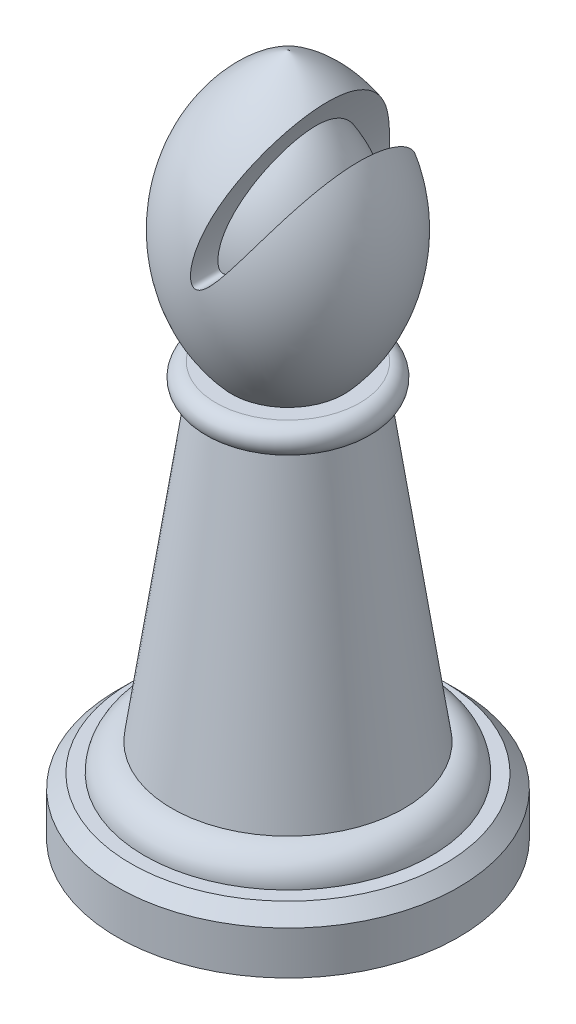
SolidWorks part; units mm, degrees
ref_plane "Front Plane" through (0, 0, 0) normal (0, 0, 1) x (1, 0, 0)
ref_plane "Top Plane" through (0, 0, 0) normal (0, 1, 0) x (1, 0, 0)
ref_plane "Right Plane" through (0, 0, 0) normal (1, 0, 0) x (0, 0, -1)
sketch "Sketch2" plane through (0, 0, 0) normal (0, 0, 1) x (1, 0, 0)
  line L0 (0, 0) -> (-9.525, 0)
  line L1 (-9.525, 0) -> (-9.525, 3.175)
  line L2 (-9.525, 3.175) -> (-8.001, 3.175)
  line L3 (-8.001, 3.175) -> (-8.001, 4.699)
  line L4 (-8.001, 4.699) -> (-6.477, 4.699)
  line L5 (-6.477, 4.699) -> (-4.0386, 21.5392)
  line L6 (-4.0386, 21.5392) -> (-4.7752, 21.5392) construction
  line L7 (-4.7752, 21.5392) -> (-4.7752, 22.301) construction
  line L8 (-4.013, 23.0632) -> (-3.1496, 23.0632)
  line L9 (0, 0) -> (0, 38.1)
  line L10 (-4.7752, 22.301) -> (-4.7752, 23.0632) construction
  line L11 (-4.7752, 23.0632) -> (-4.013, 23.0632) construction
  arc A0 (-3.1496, 23.0632) -> (0, 38.1) centre (3.9376, 29.427) cw
  arc A1 (-4.013, 23.0632) -> (-4.0386, 21.5392) centre (-4.013, 22.301) ccw
  dimension "D12" = 9.525
  dimension "D1" = 38.1
  dimension "D2" = 9.525
  dimension "D3" = 3.175
  dimension "D4" = 1.524
  dimension "D5" = 1.524
  dimension "D6" = 1.524
  dimension "D7" = 21.5392
  dimension "D8" = 1.524
  dimension "D9" = 4.7752
  dimension "D10" = 4.0386
  dimension "D11" = 3.1496
revolve "Revolve1" add sketch "Sketch2" angle 360 about L9
fillet "Fillet1" radius 1.524 1 edges at (0, 4.699, -8.001)
chamfer "Chamfer1" distance 0.762 angle 45 1 edges at (0, 3.175, -9.525)
sketch "Sketch3" plane through (0, 0, 0) normal (0, 0, 1) x (1, 0, 0)
  arc A0 (3.1496, 23.0632) -> (0, 38.1) centre (-3.9376, 29.427) ccw construction
  ellipse E0 centre (3.136, 35.8058) end of major axis (5.9336, 42.0534) minor radius 1.2192
  dimension "D1" = 13.6906
  dimension "D2" = 2.4384
extrude "Cut-Extrude1" cut sketch "Sketch3" against normal through all both and the other way through all
sketch "Sketch4" plane through (0, 0, 0) normal (0, 0, 1) x (1, 0, 0)
  line L0 (0, 36.392) -> (0, 24.0814)
  line L1 (0, 38.1) -> (0, 36.392) construction
  line L2 (-2.0157, 24.0814) -> (0, 24.0814)
  arc A1 (0.63, 36.7123) -> (0, 36.392) centre (3.9376, 29.427) ccw construction
  arc A2 (0.63, 36.7123) -> (-2.0157, 24.0814) centre (3.9376, 29.427) ccw
  arc A3 (0, 36.392) -> (-2.0157, 24.0814) centre (3.9376, 29.427) ccw
  dimension "D1" = 1.524
revolve "Revolve2" add sketch "Sketch4" angle 360 about L1
